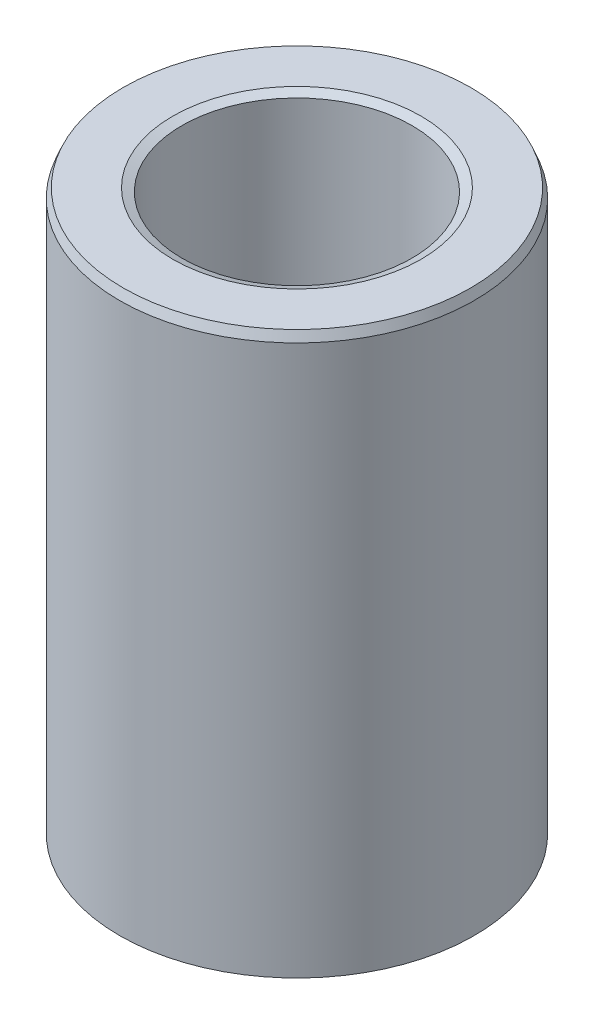
SolidWorks part; units mm, degrees
ref_plane "Front Plane" through (0, 0, 0) normal (0, 0, 1) x (1, 0, 0)
ref_plane "Top Plane" through (0, 0, 0) normal (0, 1, 0) x (1, 0, 0)
ref_plane "Right Plane" through (0, 0, 0) normal (1, 0, 0) x (0, 0, -1)
sketch "Sketch1" plane through (0, 0, 0) normal (0, 1, 0) x (1, 0, 0)
  circle A0 centre (0, 0) radius 35
  dimension "SLEEVE_OD" = 70
extrude "Boss-Extrude1" add sketch "Sketch1" along normal blind 111.0791
sketch "Sketch2" plane through (0, 0, 0) normal (0, 1, 0) x (1, 0, 0)
  circle A0 centre (0, 0) radius 22.699
  dimension "BORE_D" = 45.3979
extrude "Cut-Extrude1" cut sketch "Sketch2" along normal through all
chamfer "Chamfer1" distance 1.7968 angle 21.582 4 edges at (0, 111.0791, 22.699) (0, 0, 22.699) (0, 0, 35) (0, 111.0791, 35) first distance on face at (0, 111.0791, 22.699) first distance on face at (0, 0, 22.699) first distance on face at (0, 111.0791, 35)
